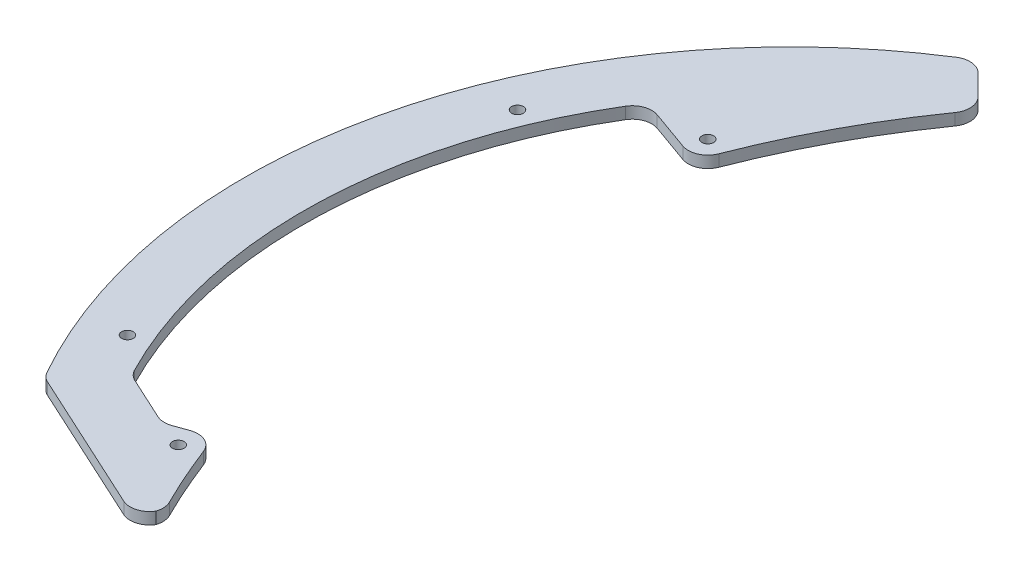
SolidWorks part; units mm, degrees
material "1060 Alloy"
ref_plane "Front Plane" through (0, 0, 0) normal (0, 0, 1) x (1, 0, 0)
ref_plane "Top Plane" through (0, 0, 0) normal (0, 1, 0) x (1, 0, 0)
ref_plane "Right Plane" through (0, 0, 0) normal (1, 0, 0) x (0, 0, -1)
sketch "Sketch1" plane through (0, 0, 0) normal (0, 1, 0) x (1, 0, 0)
  circle A0 centre (0, 0) radius 140
  dimension "D1" = 280
extrude "Boss-Extrude1" add sketch "Sketch1" along normal blind 3
sketch "Sketch19" plane through (0, 3, 0) normal (0, 1, 0) x (1, 0, 0)
  line L0 (-78.4889, 78.4889) -> (78.4889, -78.4889) construction
  line L1 (111, 45.9777) -> (45.9777, 111) construction
  line L2 (45.9777, 111) -> (-45.9777, 111) construction
  line L3 (-45.9777, 111) -> (-111, 45.9777) construction
  line L4 (-111, 45.9777) -> (-111, -45.9777) construction
  line L5 (-111, -45.9777) -> (-45.9777, -111) construction
  line L6 (-45.9777, -111) -> (45.9777, -111) construction
  line L7 (45.9777, -111) -> (111, -45.9777) construction
  line L8 (111, -45.9777) -> (111, 45.9777) construction
  line L9 (78.4889, 78.4889) -> (-78.4889, -78.4889) construction
  circle A0 centre (-89.0955, -67.8823) radius 1.5
  circle A1 centre (-89.0955, 67.8823) radius 1.5
  circle A2 centre (89.0955, 67.8823) radius 1.5
  circle A3 centre (89.0955, -67.8823) radius 1.5
  circle A4 centre (0, 0) radius 111 construction
  circle A5 centre (-67.8823, 89.0955) radius 1.5
  circle A6 centre (67.8823, 89.0955) radius 1.5
  circle A7 centre (67.8823, -89.0955) radius 1.5
  circle A8 centre (-67.8823, -89.0955) radius 1.5
  dimension "D5" = 3
  dimension "D1" = 15
  dimension "D6" = 111
extrude "Cut-Extrude3" cut sketch "Sketch19" against normal up to next
sketch "Sketch17" plane through (0, 0, 0) normal (0, -1, 0) x (1, 0, 0)
  line L0 (-50, 100) -> (-121.2436, 70)
  line L1 (-50, 100) -> (50, 100)
  line L2 (-121.2436, 70) -> (-121.2436, 140)
  line L3 (-121.2436, 140) -> (121.2436, 140)
  line L4 (121.2436, 140) -> (121.2436, 70)
  line L5 (121.2436, 70) -> (50, 100)
  circle A0 centre (0, 0) radius 140 construction
  dimension "D1" = 100
  dimension "D2" = 50
  dimension "D3" = 50
  dimension "D4" = 70
extrude "Cut-Extrude1" [suppressed] cut sketch "Sketch17" against normal up to next
sketch "Sketch25" plane through (0, 3, 0) normal (0, 1, 0) x (1, 0, 0)
  circle A0 centre (-120, 50) radius 1.5
  circle A1 centre (-120, -50) radius 1.5
  dimension "D1" = 3
  dimension "D2" = 50
  dimension "D3" = 50
  dimension "D4" = 120
extrude "Cut-Extrude10" cut sketch "Sketch25" against normal up to next
sketch "Sketch20" plane through (0, 3, 0) normal (0, 1, 0) x (1, 0, 0)
  line L0 (-72, 120.0666) -> (-50, 98.0666)
  line L1 (-50, 98.0666) -> (50, 98.0666)
  line L2 (50, 98.0666) -> (72, 120.0666)
  circle A1 centre (0, 0) radius 140 construction
  dimension "D1" = 144
  dimension "D2" = 100
  dimension "D3" = 50
extrude "Cut-Extrude4" cut sketch "Sketch20" against normal up to next
fillet "Fillet2" radius 10 2 edges at (50, 1.5, -98.0666) (-50, 1.5, -98.0666)
sketch "Sketch26" plane through (0, 3, 0) normal (0, 1, 0) x (1, 0, 0)
  line L0 (-121.2436, -70) -> (-79.057, -89.4493)
  line L1 (-79.057, -89.4493) -> (-76.4598, -83.816)
  line L2 (-96.1026, -65.0734) -> (-86.1288, -61.5152)
  line L3 (-86.1288, -61.5152) -> (-93.657, -40.4132) construction
  line L4 (-104.7766, 68.1679) -> (-86.1288, 61.5152)
  line L5 (-60.85, 108.9167) -> (-72, 120.0666)
  line L6 (-72, 120.0666) -> (-52.9289, 100.9956) construction
  line L7 (-86.1288, 61.5152) -> (-98.4946, 26.8531) construction
  line L8 (-110.5001, -58.4357) -> (-96.1026, -65.0734)
  circle A0 centre (-67.8823, 89.0955) radius 5 construction
  circle A1 centre (-89.0955, 67.8823) radius 5 construction
  circle A2 centre (-120, 50) radius 5 construction
  circle A3 centre (-89.0955, -67.8823) radius 5 construction
  circle A4 centre (-67.8823, -89.0955) radius 5 construction
  circle A5 centre (-120, -50) radius 5 construction
  arc A6 (-110.5001, -58.4357) -> (-104.7766, 68.1679) centre (0, 0) cw
  arc A7 (-72, 120.0666) -> (72, 120.0666) centre (0, 0) ccw construction
  arc A8 (-86.1288, -61.5152) -> (-76.4598, -83.816) centre (86.3028, 0) ccw
  arc A9 (-86.1288, 61.5152) -> (-60.85, 108.9167) centre (86.3028, 0) cw
  dimension "D1" = 10
  dimension "D4" = 15
  dimension "D2" = 70
  dimension "D3" = 10
extrude "Cut-Extrude11" cut sketch "Sketch26" against normal through all and the other way through all flip side to cut body kept at (-86.1288, 3, -61.5152)
sketch "Sketch23" [suppressed] plane through (0, 3, 0) normal (0, 1, 0) x (1, 0, 0)
  line L0 (-72.365, -73.9737) -> (-80.4987, -93.2894)
  line L1 (-72, 120.0666) -> (-52.9289, 100.9956) construction
  line L2 (-121.2436, -70) -> (-50, -100) construction
  arc A0 (-54.9334, 103) -> (-72.365, -73.9737) centre (114.6363, -3.0477) ccw
  arc A3 (-72.365, -73.9737) -> (-54.9334, -109.0955) centre (114.6363, -3.0477) ccw construction
  circle A4 centre (-67.8823, -89.0955) radius 1.5 construction
  dimension "D1" = 103
  dimension "D2" = 20
  dimension "D3" = 200
  dimension "D4" = 90
  dimension "D5" = 10
extrude "Cut-Extrude8" [suppressed] cut sketch "Sketch23" against normal through all and the other way through all
sketch "Sketch24" [suppressed] plane through (0, 3, 0) normal (0, 1, 0) x (1, 0, 0)
  line L0 (-87.2371, 61.6912) -> (-76.1181, 57.0584)
  line L1 (-108.2916, -62.4334) -> (-85.8817, -71.87)
  line L3 (-121.2436, -70) -> (-78.3054, -88.0808) construction
  line L4 (-88.8916, -62.3806) -> (-77.7417, -57.7349)
  line L5 (-120, 50) -> (0, 0) construction
  line L6 (0, 0) -> (-120, -50) construction
  line L7 (-76.1181, 57.0584) -> (-77.7417, -57.7349)
  arc A1 (-87.2371, 61.6912) -> (-67.7264, 105.0625) centre (114.6363, -3.0477) cw
  arc A2 (-54.9334, 103) -> (-72.365, -73.9737) centre (114.6363, -3.0477) ccw construction
  arc A3 (-67.7264, 105.0625) -> (-108.2916, -62.4334) centre (0, 0) ccw
  circle A4 centre (-120, 50) radius 5 construction
  circle A5 centre (-120, -50) radius 5 construction
  arc A6 (-85.8817, -71.87) -> (-88.8916, -62.3806) centre (114.6363, -3.0477) cw
  circle A8 centre (-89.0955, -67.8823) radius 1.5 construction
  circle A9 centre (-89.0955, 67.8823) radius 1.5 construction
  dimension "D2" = 10
  dimension "D3" = 5
  dimension "D4" = 12
  dimension "D5" = 12
  dimension "D1" = 5
  dimension "D6" = 12
extrude "Cut-Extrude9" [suppressed] cut sketch "Sketch24" against normal up to next
fillet "Fillet4" [suppressed] radius 5
fillet "Fillet5" [suppressed] radius 3
fillet "Fillet6" radius 5 10 edges at (-72, 1.5, -120.0666) (-121.2436, 1.5, 70) (-79.057, 1.5, 89.4493) (-76.4598, 1.5, 83.816) (-86.1288, 1.5, 61.5152) (-104.7766, 1.5, -68.1679) (-86.1288, 1.5, -61.5152) (-60.85, 1.5, -108.9167) (-110.5001, 1.5, 58.4357) (-96.1026, 1.5, 65.0734)
equation "\"D3@Sketch20\" = \"D2@Sketch20\" / 2"
